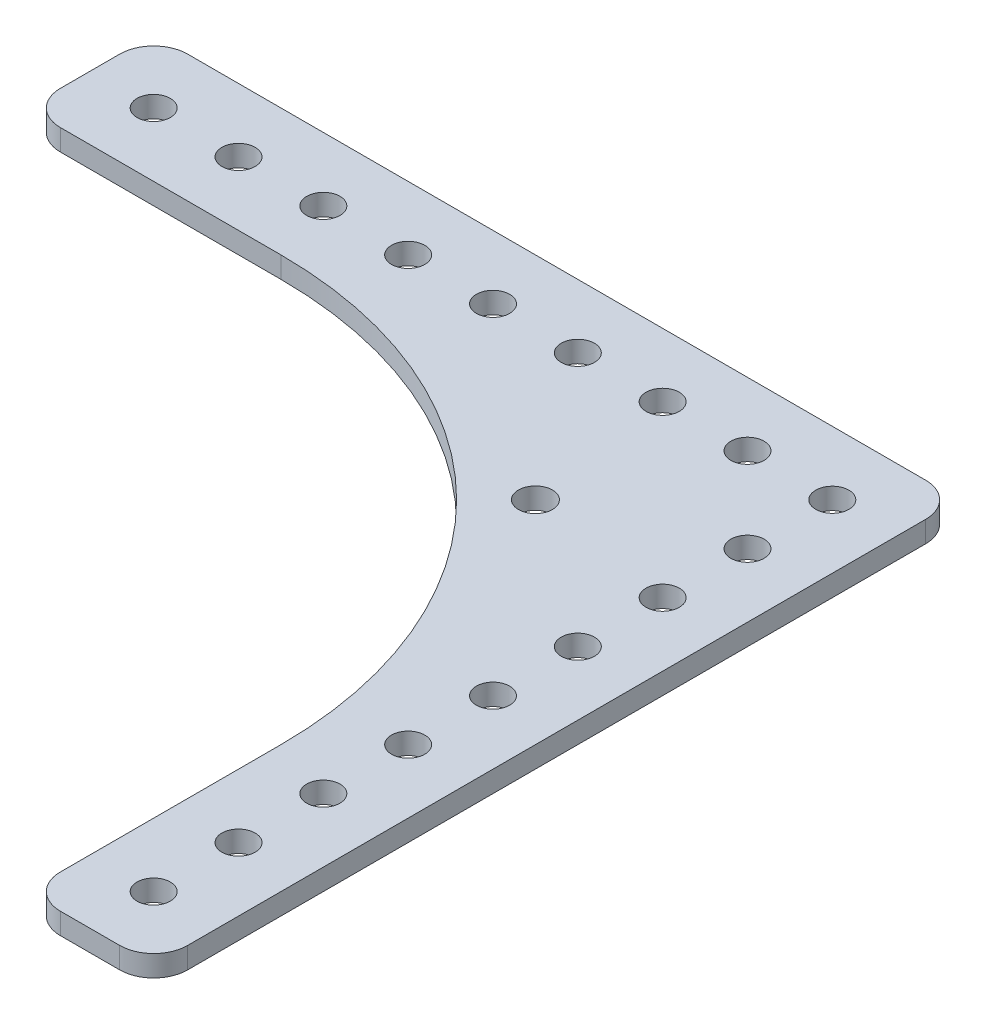
SolidWorks part; units mm, degrees
ref_plane "Front Plane" through (0, 0, 0) normal (0, 0, 1) x (1, 0, 0)
ref_plane "Top Plane" through (0, 0, 0) normal (0, 1, 0) x (1, 0, 0)
ref_plane "Right Plane" through (0, 0, 0) normal (1, 0, 0) x (0, 0, -1)
sketch "Sketch1" plane through (0, 0, 0) normal (0, 1, 0) x (1, 0, 0)
  line B0 (0, 63.5) -> (-33.02, 63.5)
  line B1 (-38.1, 68.58) -> (-38.1, 77.47)
  line B2 (-33.02, 82.55) -> (77.47, 82.55)
  line B3 (82.55, 77.47) -> (82.55, -33.02)
  line B4 (77.47, -38.1) -> (68.58, -38.1)
  line B5 (63.5, -33.02) -> (63.5, 0)
  arc B6 (0, 63.5) -> (63.5, 0) centre (0, 0) cw
  arc B7 (68.58, -38.1) -> (63.5, -33.02) centre (68.58, -33.02) cw
  arc B8 (82.55, -33.02) -> (77.47, -38.1) centre (77.47, -33.02) cw
  arc B9 (77.47, 82.55) -> (82.55, 77.47) centre (77.47, 77.47) cw
  arc B10 (-38.1, 77.47) -> (-33.02, 82.55) centre (-33.02, 77.47) cw
  arc B11 (-33.02, 63.5) -> (-38.1, 68.58) centre (-33.02, 68.58) cw
  circle B12 centre (-28.575, 73.025) radius 2.4892
  circle B13 centre (-15.875, 73.025) radius 2.4892
  circle B14 centre (-3.175, 73.025) radius 2.4892
  circle B15 centre (9.525, 73.025) radius 2.4892
  circle B16 centre (22.225, 73.025) radius 2.4892
  circle B17 centre (34.925, 73.025) radius 2.4892
  circle B18 centre (47.625, 73.025) radius 2.4892
  circle B19 centre (60.325, 73.025) radius 2.4892
  circle B20 centre (73.025, 73.025) radius 2.4892
  circle B21 centre (73.025, 60.325) radius 2.4892
  circle B22 centre (73.025, 47.625) radius 2.4892
  circle B23 centre (73.025, 34.925) radius 2.4892
  circle B24 centre (73.025, 22.225) radius 2.4892
  circle B25 centre (73.025, 9.525) radius 2.4892
  circle B26 centre (73.025, -3.175) radius 2.4892
  circle B27 centre (73.025, -15.875) radius 2.4892
  circle B28 centre (73.025, -28.575) radius 2.4892
  circle B29 centre (50.8, 50.8) radius 2.54
sketch_block_instance "Block-Bumper_Gussest-1"
sketch_block "Block-Bumper_Gussest" parameters "D1"=63.5, "D2"=5.08, "D3"=4.9784, "D8"=5.08, "D4"=9.525, "D5"=9.525, "D6"=12.7, "D7"=9.525, "D9"=31.75, "D10"=31.75
extrude "Boss-Extrude1" add sketch "Sketch1" along normal blind 3.175
